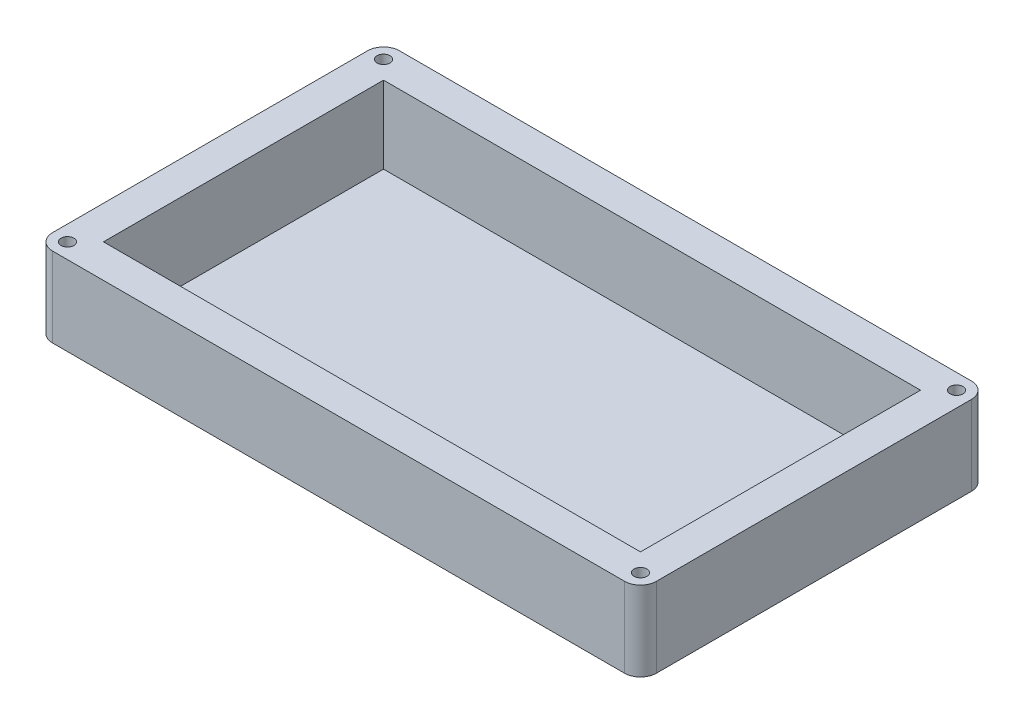
SolidWorks part; units mm, degrees
ref_plane "Plan de face" through (0, 0, 0) normal (0, 0, 1) x (1, 0, 0)
ref_plane "Plan de dessus" through (0, 0, 0) normal (0, 1, 0) x (1, 0, 0)
ref_plane "Plan de droite" through (0, 0, 0) normal (1, 0, 0) x (0, 0, -1)
sketch "Esquisse1" plane through (0, 0, 0) normal (0, 1, 0) x (1, 0, 0)
  line L1 (-111.3, -67.5) -> (111.3, -67.5)
  line L2 (-117.5, -61.3) -> (-117.5, 61.3)
  line L3 (-111.3, 67.5) -> (111.3, 67.5)
  line L4 (117.5, -61.3) -> (117.5, 61.3)
  line L5 (-117.5, -67.5) -> (117.5, 67.5) construction
  line L6 (-117.5, 67.5) -> (117.5, -67.5) construction
  arc A0 (117.5, -61.3) -> (111.3, -67.5) centre (111.3, -61.3) cw
  arc A1 (117.5, 61.3) -> (111.3, 67.5) centre (111.3, 61.3) ccw
  arc A2 (-117.5, -61.3) -> (-111.3, -67.5) centre (-111.3, -61.3) ccw
  arc A3 (-117.5, 61.3) -> (-111.3, 67.5) centre (-111.3, 61.3) cw
  point P0 (0, 0)
  dimension "D3" = 6.2
  dimension "D1" = 135
  dimension "D2" = 235
extrude "Boss.-Extru.1" add sketch "Esquisse1" against normal blind 1 contours A3 L2 A2 L1 A0 L4 A1 L3 region at (0, 0, 0)
sketch "Esquisse3" plane through (0, -1, 0) normal (0, -1, 0) x (1, 0, 0)
  line L0 (117.5, 61.3) -> (117.5, -61.3) construction
  line L1 (-111.3, -67.5) -> (111.3, -67.5)
  line L2 (-117.5, -61.3) -> (-117.5, 61.3)
  line L3 (-111.3, 67.5) -> (111.3, 67.5)
  line L4 (117.5, -61.3) -> (117.5, 61.3)
  line L5 (-117.5, -67.5) -> (117.5, 67.5) construction
  line L6 (-117.5, 67.5) -> (117.5, -67.5) construction
  line L7 (-111.3, 67.5) -> (111.3, 67.5) construction
  arc A0 (117.5, 61.3) -> (111.3, 67.5) centre (111.3, 61.3) ccw
  arc A1 (111.3, -67.5) -> (117.5, -61.3) centre (111.3, -61.3) ccw
  arc A2 (-111.3, -67.5) -> (-117.5, -61.3) centre (-111.3, -61.3) cw
  arc A3 (-117.5, 61.3) -> (-111.3, 67.5) centre (-111.3, 61.3) cw
  point P0 (0, 0)
  dimension "D1" = 6.2
sketch "Esquisse5" plane through (0, 0, 0) normal (0, 1, 0) x (1, 0, 0)
  line L0 (117.5, -61.3) -> (117.5, 61.3) construction
  line L1 (-111.3, 67.5) -> (111.3, 67.5)
  line L2 (-117.5, 61.3) -> (-117.5, -61.3)
  line L3 (-111.3, -67.5) -> (111.3, -67.5)
  line L4 (117.5, 61.3) -> (117.5, -61.3)
  line L5 (-117.5, 67.5) -> (117.5, -67.5) construction
  line L6 (-117.5, -67.5) -> (117.5, 67.5) construction
  line L7 (-111.3, -67.5) -> (111.3, -67.5) construction
  line L8 (-111.3, 67.5) -> (111.3, 67.5) construction
  line L9 (-104.5, 54.5) -> (104.5, 54.5)
  line L10 (-104.5, 54.5) -> (-104.5, -54.5)
  line L11 (-104.5, -54.5) -> (104.5, -54.5)
  line L12 (104.5, 54.5) -> (104.5, -54.5)
  line L13 (-104.5, 54.5) -> (104.5, -54.5) construction
  line L14 (-104.5, -54.5) -> (104.5, 54.5) construction
  arc A0 (117.5, 61.3) -> (111.3, 67.5) centre (111.3, 61.3) ccw
  arc A1 (117.5, -61.3) -> (111.3, -67.5) centre (111.3, -61.3) cw
  arc A2 (-117.5, -61.3) -> (-111.3, -67.5) centre (-111.3, -61.3) ccw
  arc A3 (-111.3, 67.5) -> (-117.5, 61.3) centre (-111.3, 61.3) ccw
  point P0 (0, 0)
  point P22 (0, 0)
  dimension "D1" = 6.2
  dimension "D2" = 209
  dimension "D3" = 109
extrude "Boss.-Extru.3" add sketch "Esquisse5" along normal blind 20
sketch "Esquisse8" plane through (0, 0, 0) normal (0, 1, 0) x (1, 0, 0)
  line L0 (-111.3, 67.5) -> (111.3, 67.5) construction
  line L1 (-117.5, 61.3) -> (-117.5, -61.3) construction
  line L2 (0, 67.5) -> (0, 59.5899) construction
  line L3 (-117.5, 0) -> (-108.938, 0) construction
  line L4 (-117.5, -61.3) -> (-117.5, 61.3) construction
  line L5 (-111.5, 61.5) -> (-111.5, 55.7806) construction
  circle A0 centre (-111.5, 61.5) radius 2.2
  arc A1 (-110.3054, 59.6526) -> (-112.6946, 59.6526) centre (-111.5, 56.8927) ccw
  arc A2 (-113.6972, 61.3892) -> (-112.5026, 63.4582) centre (-115.4901, 63.8037) ccw
  arc A3 (-110.4974, 63.4582) -> (-109.3028, 61.3892) centre (-107.5099, 63.8037) ccw
  arc A4 (110.4974, 63.4582) -> (109.3028, 61.3892) centre (107.5099, 63.8037) cw
  arc A5 (113.6972, 61.3892) -> (112.5026, 63.4582) centre (115.4901, 63.8037) cw
  arc A6 (110.3054, 59.6526) -> (112.6946, 59.6526) centre (111.5, 56.8927) cw
  circle A7 centre (111.5, 61.5) radius 2.2
  circle A8 centre (111.5, -61.5) radius 2.2
  arc A9 (110.3054, -59.6526) -> (112.6946, -59.6526) centre (111.5, -56.8927) ccw
  arc A10 (113.6972, -61.3892) -> (112.5026, -63.4582) centre (115.4901, -63.8037) ccw
  arc A11 (110.4974, -63.4582) -> (109.3028, -61.3892) centre (107.5099, -63.8037) ccw
  arc A12 (-110.4974, -63.4582) -> (-109.3028, -61.3892) centre (-107.5099, -63.8037) cw
  arc A13 (-113.6972, -61.3892) -> (-112.5026, -63.4582) centre (-115.4901, -63.8037) cw
  arc A14 (-110.3054, -59.6526) -> (-112.6946, -59.6526) centre (-111.5, -56.8927) cw
  circle A15 centre (-111.5, -61.5) radius 2.2
  point P17 (-111.5, 59.3)
  point P18 (-111.5, 59.9)
  dimension "D1" = 6
  dimension "D3" = 0.6
  dimension "D4" = 4.4
  dimension "D2" = 6
  dimension "D5" = 3
extrude "Enlèv. mat.-Extru.1" cut sketch "Esquisse8" along normal up to next contours A3 A0 A2 A1 | A7 A6 A5 A4 | A15 A13 A12 A14 | A11 A8 A10 A9 region at (-111.5, 0, -61.5) region at (111.5, 0, -61.5) region at (111.5, 0, 61.5) region at (-111.5, 0, 61.5)
sketch "Esquisse9" plane through (0, 20, 0) normal (0, 1, 0) x (1, 0, 0)
  line L0 (111.3, 67.5) -> (-111.3, 67.5) construction
  line L1 (-104.5, -54.5) -> (104.5, -54.5)
  line L2 (-104.5, -54.5) -> (-104.5, 54.5)
  line L3 (-104.5, 54.5) -> (104.5, 54.5)
  line L4 (104.5, -54.5) -> (104.5, 54.5)
  line L5 (-111.5, -67.5) -> (111.5, -67.5)
  line L6 (-117.5, -61.5) -> (-117.5, 61.5)
  line L7 (-111.5, 67.5) -> (111.5, 67.5)
  line L8 (117.5, -61.5) -> (117.5, 61.5)
  line L9 (-117.5, -67.5) -> (117.5, 67.5) construction
  line L10 (-117.5, 67.5) -> (117.5, -67.5) construction
  line L11 (-117.5, 61.3) -> (-117.5, -61.3) construction
  arc A0 (111.5, -67.5) -> (117.5, -61.5) centre (111.5, -61.5) ccw
  arc A1 (117.5, 61.5) -> (111.5, 67.5) centre (111.5, 61.5) ccw
  arc A2 (-117.5, -61.5) -> (-111.5, -67.5) centre (-111.5, -61.5) ccw
  arc A3 (-111.5, 67.5) -> (-117.5, 61.5) centre (-111.5, 61.5) ccw
  circle A4 centre (-111.5, 61.5) radius 2.5
  circle A5 centre (111.5, 61.5) radius 2.5
  circle A6 centre (111.5, -61.5) radius 2.5
  circle A7 centre (-111.5, -61.5) radius 2.5
  point P4 (0, 0)
  arc M9 (-113.6972, -61.3892) -> (-112.6946, -59.6526) centre (-111.5, -61.5) cw
  arc M11 (-110.3054, -59.6526) -> (-109.3028, -61.3892) centre (-111.5, -61.5) cw
  arc M13 (-110.4974, -63.4582) -> (-112.5026, -63.4582) centre (-111.5, -61.5) cw
  arc M16 (-109.3028, 61.3892) -> (-110.3054, 59.6526) centre (-111.5, 61.5) cw
  arc M18 (-112.6946, 59.6526) -> (-113.6972, 61.3892) centre (-111.5, 61.5) cw
  arc M20 (-112.5026, 63.4582) -> (-110.4974, 63.4582) centre (-111.5, 61.5) cw
  arc M21 (117.5, 61.3) -> (111.3, 67.5) centre (111.3, 61.3) ccw
  line M22 (111.3, 67.5) -> (-111.3, 67.5)
  arc M23 (-111.3, 67.5) -> (-117.5, 61.3) centre (-111.3, 61.3) ccw
  line M24 (-117.5, 61.3) -> (-117.5, -61.3)
  arc M25 (-117.5, -61.3) -> (-111.3, -67.5) centre (-111.3, -61.3) ccw
  line M26 (-111.3, -67.5) -> (111.3, -67.5)
  arc M27 (111.3, -67.5) -> (117.5, -61.3) centre (111.3, -61.3) ccw
  line M28 (117.5, -61.3) -> (117.5, 61.3)
  line M29 (-104.5, 54.5) -> (104.5, 54.5)
  line M30 (104.5, 54.5) -> (104.5, -54.5)
  line M31 (104.5, -54.5) -> (-104.5, -54.5)
  line M32 (-104.5, -54.5) -> (-104.5, 54.5)
  arc M34 (109.3028, -61.3892) -> (110.3054, -59.6526) centre (111.5, -61.5) cw
  arc M36 (112.6946, -59.6526) -> (113.6972, -61.3892) centre (111.5, -61.5) cw
  arc M38 (112.5026, -63.4582) -> (110.4974, -63.4582) centre (111.5, -61.5) cw
  arc M39 (110.3054, 59.6526) -> (109.3028, 61.3892) centre (111.5, 61.5) cw
  arc M41 (110.4974, 63.4582) -> (112.5026, 63.4582) centre (111.5, 61.5) cw
  arc M43 (113.6972, 61.3892) -> (112.6946, 59.6526) centre (111.5, 61.5) cw
  dimension "D1" = 6
  dimension "D2" = 5
  dimension "D3" = 5
  dimension "D4" = 5
  dimension "D5" = 5
extrude "Boss.-Extru.4" add sketch "Esquisse9" along normal blind 10 contours A7 A6 A5 A4 M28 M21 M22 M23 M24 M25 M26 M27 M13 M9 M11 M38 M34 M36 M43 M39 M41 M16 M18 M20 M32 M29 M30 M31 region at (-113.7677, 20, 63.7677)
chamfer "Chanfrein1" distance 1 angle 45 4 edges at (111.5, 20, 64) (111.5, 20, -59) (-111.5, 20, -59) (-111.5, 20, 64)
